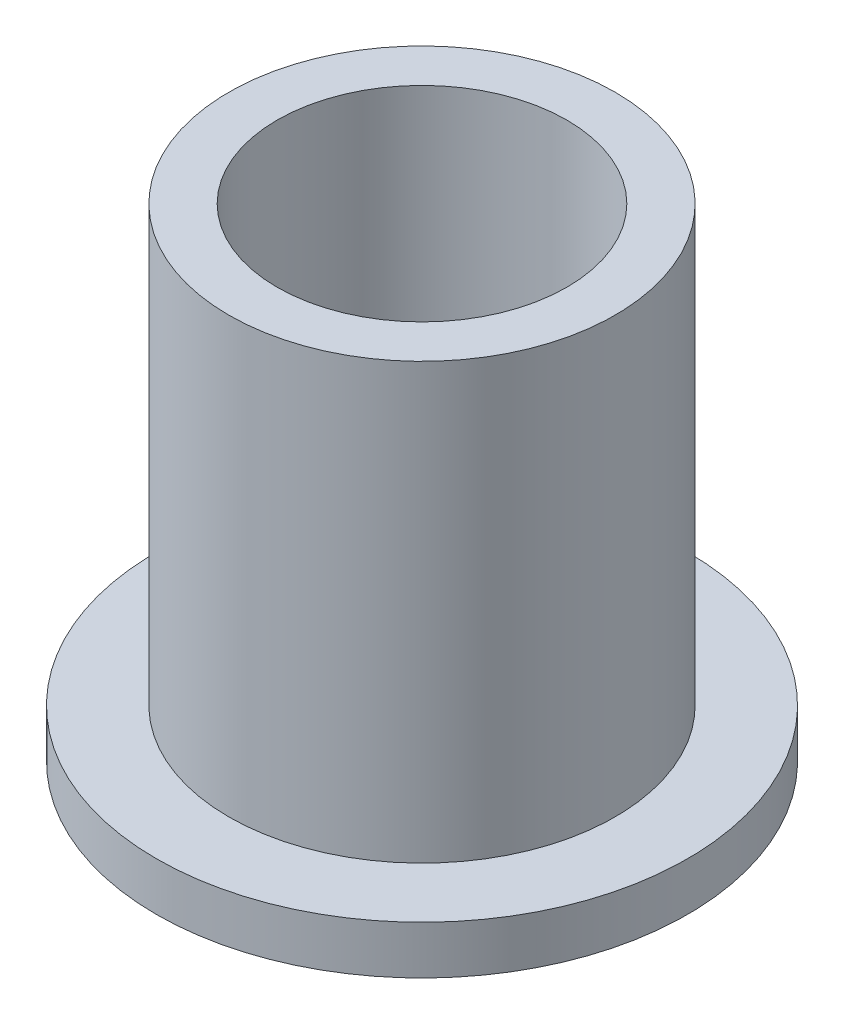
SolidWorks part; units mm, degrees
material "Polyethylene Cross-Linked"
ref_plane "Front" through (0, 0, 0) normal (0, 0, 1) x (1, 0, 0)
ref_plane "Top" through (0, 0, 0) normal (0, 1, 0) x (1, 0, 0)
ref_plane "Right" through (0, 0, 0) normal (1, 0, 0) x (0, 0, -1)
sketch "Sketch1" plane through (0, 0, 0) normal (0, 1, 0) x (1, 0, 0)
  line L0 (0, 6) -> (0, 8) construction
  circle A0 centre (0, 0) radius 6
  circle A1 centre (0, 0) radius 8
  circle A2 centre (0, 0) radius 11
  point P7 (0, 6.6667)
  dimension "ID" = 12
  dimension "OD" = 16
  dimension "FlangeOD" = 22
  dimension "D1" = 2
  dimension "D2" = 0.6667
sketch "Sketch2" plane through (0, 0, 0) normal (0, 1, 0) x (1, 0, 0)
  circle A0 centre (0, 0) radius 6 construction
  circle A1 centre (0, 0) radius 8 construction
  circle A2 centre (0, 0) radius 6
  circle A3 centre (0, 0) radius 8
extrude "Boss-Extrude1" add sketch "Sketch2" along normal blind 20
sketch "Sketch3" plane through (0, 0, 0) normal (0, 1, 0) x (1, 0, 0)
  circle A0 centre (0, 0) radius 11 construction
  circle A1 centre (0, 0) radius 8 construction
  circle A2 centre (0, 0) radius 11
  circle A3 centre (0, 0) radius 8
extrude "Boss-Extrude2" add sketch "Sketch3" along normal blind 2
sketch "Sketch4" plane through (0, 0, 0) normal (1, 0, 0) x (0, 0, -1)
  line L0 (0, 0) -> (0, 20) construction
  line L1 (11, 0) -> (11, 2) construction
  line L3 (6.1524, 20) -> (6.0762, 20)
  line L4 (6.0762, 0.0762) -> (6.0762, 20)
  line L5 (6.0762, 0.0762) -> (11, 0.0762)
  line L6 (11, 0.0762) -> (11, 0.1524)
  line L7 (11, 0.1524) -> (6.1524, 0.1524)
  line L8 (6.1524, 0.1524) -> (6.1524, 20)
  line L9 (-11, 0) -> (11, 0) construction
  line L10 (8, 20) -> (-8, 20) construction
  line L12 (6, 20) -> (6, 0) construction
  line L13 (6, 20) -> (-6, 20) construction
  dimension "D1" = 0.0762
  dimension "D2" = 0.0762
  dimension "D3" = 0.0762
ref_plane "Contact Plane 1" through (0, 20, 0) normal (0, 1, 0) x (1, 0, 0)
ref_plane "Contact Plane 2" through (0, 0, 0) normal (0, -1, 0) x (-1, 0, 0)
ref_axis "Center Axis 1" through (0, 20, 0) along (0, -1, 0)
equation "\"D2@Sketch1\" = \"D1@Sketch1\"/3"
